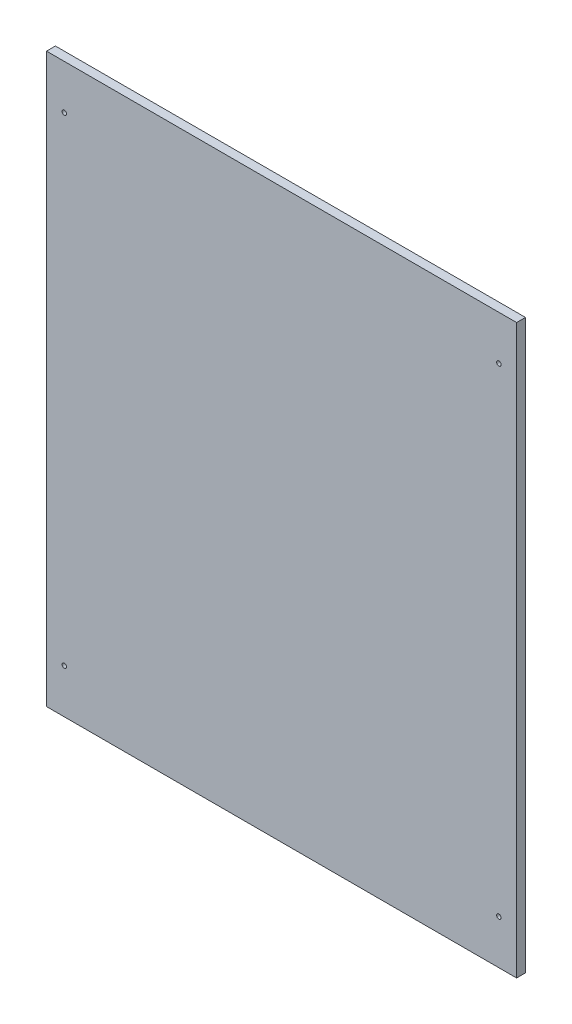
SolidWorks part; units mm, degrees
ref_plane "Спереди" through (0, 0, 0) normal (0, 0, 1) x (1, 0, 0)
ref_plane "Сверху" through (0, 0, 0) normal (0, 1, 0) x (1, 0, 0)
ref_plane "Справа" through (0, 0, 0) normal (1, 0, 0) x (0, 0, -1)
sketch "Эскиз3" plane through (0, 0, 0) normal (0, 0, 1) x (1, 0, 0)
  line L5 (265, -320) -> (-265, -320)
  line L6 (265, -320) -> (265, 320)
  line L7 (265, 320) -> (-265, 320)
  line L8 (-265, -320) -> (-265, 320)
  point P0 (0, 0)
  point P5 (-265, 0)
  point P6 (0, 320)
  dimension "D1" = 640
  dimension "D2" = 530
extrude "Бобышка-Вытянуть1" add sketch "Эскиз3" along normal blind 10
sketch "Эскиз4" plane through (0, 0, 10) normal (0, 0, 1) x (1, 0, 0)
  line L0 (265, 320) -> (-265, 320) construction
  line L1 (-265, 320) -> (-265, -320) construction
  circle A0 centre (-245, 270) radius 2.5
  dimension "D1" = 5
  dimension "D2" = 50
  dimension "D3" = 20
extrude "Вырез-Вытянуть1" cut sketch "Эскиз4" against normal through all contours A0
pattern_linear "Линейный массив1" count 2 spacing 490 along (1, 0, 0) count 2 spacing 540 along (0, -1, 0) of "Вырез-Вытянуть1"
equation "\"Ширина груза\"= 420"
equation "\"Глубина груза\"= 490"
equation "\"Высота груза\"= 297"
equation "\"Ширина ячейки\"= \"Ширина груза\" + 10"
equation "\"Глубина ячейки\"= \"Глубина груза\" + 10"
equation "\"Высота ячейки\"= \"Высота груза\" + 10 + 13"
equation "\"Колво ячеек ширина\"= 2"
equation "\"Колво ячеек высота\"= 2"
equation "\"Толщина стенки\"= 10"
equation "\"Крепление дверцы\"= 5"
equation "\"Ширина рейки\"= \"Толщина шестерни\""
equation "\"Высота рейки\"= 20"
equation "\"Высота пола\"= 20"
equation "\"Колво полозьев\"= 5"
equation "\"Отступ рейки\"= 20"
equation "\"Глубина каретки\"= \"Глубина ячейки\" + 80"
equation "\"Длинна рейки\"= ( \"Ширина ячейки\" + \"Толщина стенки\" + \"Крепление дверцы\" ) * \"Колво ячеек ширина\" + \"Ширина ячейки выгрузки\" * \"Колво выгрузки\" + \"Толщина стенки\""
equation "\"Отступ шпильки\"= 20"
equation "\"Диаметр шпильки\"= 5"
equation "\"D1@Бобышка-Вытянуть1\" = \"Толщина стенки\""
equation "\"D1@Эскиз4\"= \"Диаметр шпильки\""
equation "\"D2@Эскиз4\"=\"Отступ шпильки\" + \"Ширина рейки\""
equation "\"D3@Эскиз4\"= \"Отступ шпильки\""
equation "\"D2@Эскиз3\"=\"Ширина ячейки\" + \"Ширина пластины\" * 2"
equation "\"D1@Эскиз3\"= \"Глубина каретки\" + \"Ширина рейки\" * 2"
equation "\"D3@Линейный массив1\"=\"Ширина ячейки\"  +\"Ширина пластины\" *2 - \"Отступ шпильки\" * 2"
equation "\"D4@Линейный массив1\"=\"Глубина каретки\" + \"Ширина рейки\" * 2 - \"Отступ шпильки\" * 2 - \"Ширина рейки\" * 2"
equation "\"Длинна шпильки\"= ( \"Высота ячейки\" + \"Толщина стенки\" + \"Высота пола\" ) * \"Колво ячеек высота\" + ( \"Толщина стенки\" + \"Отступ рейки\" ) * 2"
equation "\"Ширина пластины\"= 50  "
